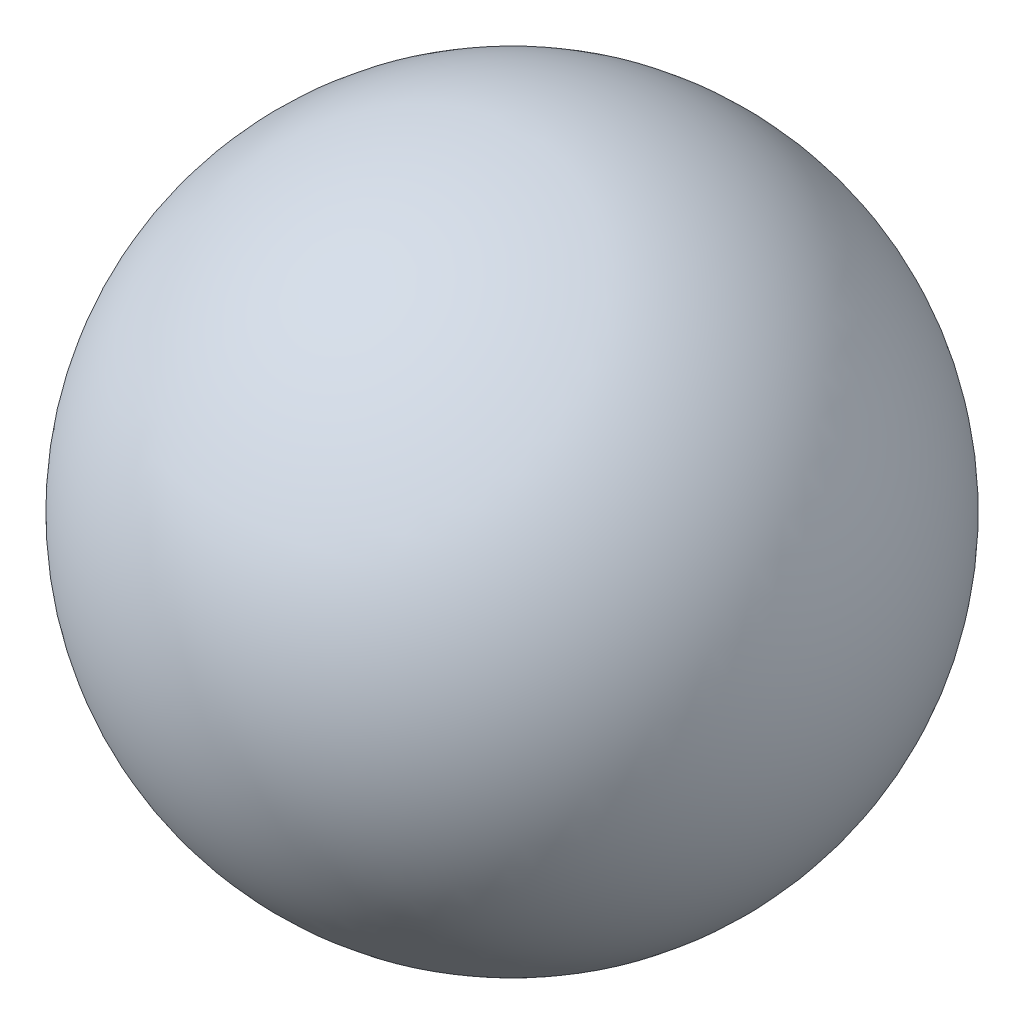
SolidWorks part; units mm, degrees
ref_plane "前视基准面" through (0, 0, 0) normal (0, 0, 1) x (1, 0, 0)
ref_plane "上视基准面" through (0, 0, 0) normal (0, 1, 0) x (1, 0, 0)
ref_plane "右视基准面" through (0, 0, 0) normal (1, 0, 0) x (0, 0, -1)
sketch "草图1" plane through (0, 0, 0) normal (0, 0, 1) x (1, 0, 0)
  line L0 (0, 124.4874) -> (0, -127.4975) construction
  line L1 (0, 108) -> (0, -108)
  arc A0 (0, -108) -> (0, 108) centre (0, 0) ccw
  dimension "D1" = 216
revolve "旋转1" add sketch "草图1" angle 360 about L0
ref_plane "基准面1" through (0, 0, 34) normal (0, 0, 1) x (1, 0, 0)
